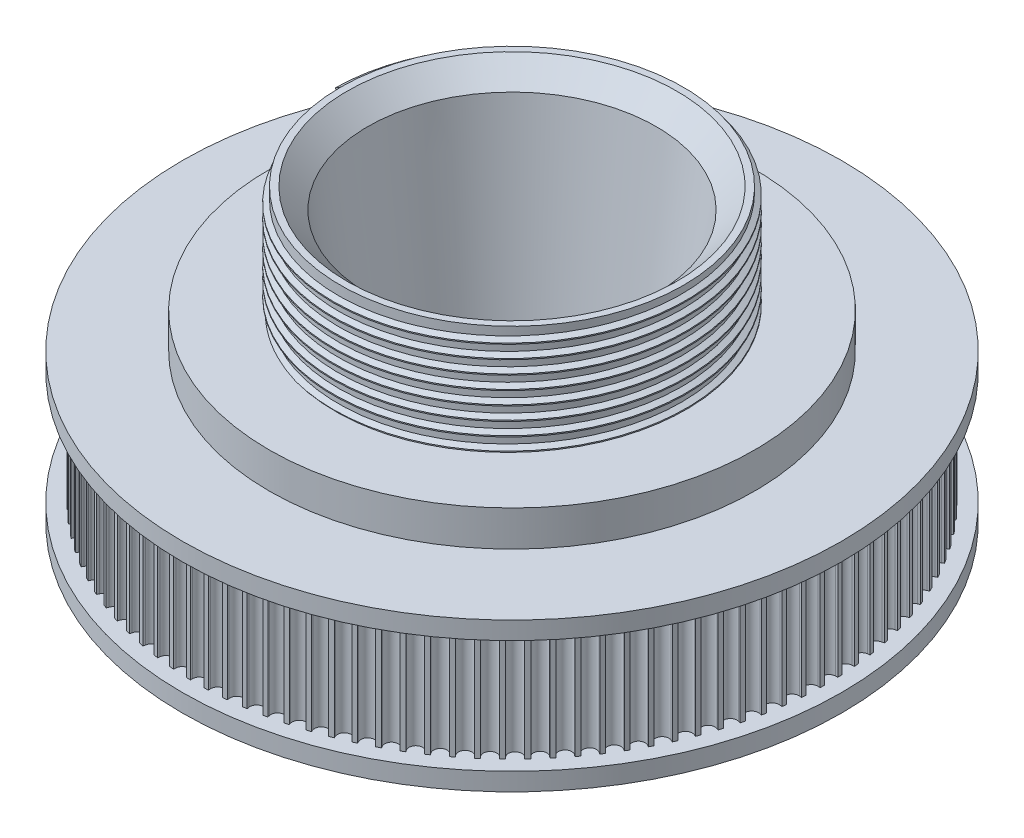
SolidWorks part; units mm, degrees
ref_plane "Front Plane" through (0, 0, 0) normal (0, 0, 1) x (1, 0, 0)
ref_plane "Top Plane" through (0, 0, 0) normal (0, 1, 0) x (1, 0, 0)
ref_plane "Right Plane" through (0, 0, 0) normal (1, 0, 0) x (0, 0, -1)
sketch "Sketch2" plane through (0, 0, 0) normal (0, 1, 0) x (1, 0, 0)
  line L2 (32.6647, -41.3108) -> (32.6647, -40.5508)
  line L3 (31.9047, -41.3108) -> (31.9047, -41.5526)
  line L5 (33.4247, -41.3108) -> (33.4247, -41.5526)
  line L6 (31.4389, -41.2976) -> (31.4252, -41.539)
  line L7 (29.9213, -41.2116) -> (29.9076, -41.453)
  line L8 (29.4569, -41.1721) -> (29.4296, -41.4123)
  line L9 (27.9467, -41.0003) -> (27.9193, -41.2406)
  line L10 (27.4853, -40.9346) -> (27.4444, -41.173)
  line L11 (25.9871, -40.6777) -> (25.9463, -40.9161)
  line L12 (25.5302, -40.586) -> (25.4759, -40.8217)
  line L13 (24.049, -40.2448) -> (23.9947, -40.4804)
  line L14 (23.598, -40.1273) -> (23.5304, -40.3595)
  line L15 (22.1384, -39.7029) -> (22.0709, -39.9351)
  line L16 (21.6948, -39.5601) -> (21.6142, -39.7881)
  line L17 (20.2616, -39.0537) -> (20.181, -39.2817)
  line L18 (19.8267, -38.8861) -> (19.7334, -39.1092)
  line L19 (18.4245, -38.2994) -> (18.3312, -38.5225)
  line L20 (17.9998, -38.1075) -> (17.894, -38.3249)
  line L21 (16.633, -37.4424) -> (16.5272, -37.6599)
  line L22 (16.2199, -37.2268) -> (16.102, -37.4379)
  line L23 (14.8929, -36.4855) -> (14.775, -36.6966)
  line L24 (14.4926, -36.2467) -> (14.3629, -36.4508)
  line L25 (13.2097, -35.4316) -> (13.08, -35.6357)
  line L26 (12.8236, -35.1706) -> (12.6826, -35.367)
  line L27 (11.5888, -34.2841) -> (11.4478, -34.4806)
  line L28 (11.2181, -34.0017) -> (11.0662, -34.1899)
  line L29 (10.0355, -33.0468) -> (9.8836, -33.235)
  line L30 (9.6813, -32.7439) -> (9.519, -32.9231)
  line L31 (8.5546, -31.7236) -> (8.3923, -31.9029)
  line L32 (8.2181, -31.4011) -> (8.0459, -31.5709)
  line L33 (7.151, -30.3188) -> (6.9788, -30.4885)
  line L34 (6.8333, -29.9778) -> (6.6517, -30.1375)
  line L35 (5.829, -28.8367) -> (5.6475, -28.9965)
  line L36 (5.5312, -28.4783) -> (5.3409, -28.6275)
  line L37 (4.5931, -27.2823) -> (4.4028, -27.4315)
  line L38 (4.316, -26.9076) -> (4.1175, -27.0458)
  line L39 (3.4471, -25.6604) -> (3.2486, -25.7987)
  line L40 (3.1916, -25.2706) -> (2.9857, -25.3974)
  line L41 (2.3946, -23.9763) -> (2.1887, -24.1031)
  line L42 (2.1616, -23.5727) -> (1.9488, -23.6876)
  line L43 (1.4392, -22.2354) -> (1.2264, -22.3503)
  line L44 (1.2293, -21.8192) -> (1.0104, -21.9219)
  line L45 (0.5837, -20.4431) -> (0.3648, -20.5458)
  line L46 (0.3978, -20.0158) -> (0.1734, -20.1059)
  line L47 (-0.169, -18.6054) -> (-0.3934, -18.6955)
  line L48 (-0.3304, -18.1682) -> (-0.5596, -18.2455)
  line L49 (-0.8165, -16.728) -> (-1.0456, -16.8053)
  line L50 (-0.953, -16.2824) -> (-1.1861, -16.3466)
  line L51 (-1.3567, -14.817) -> (-1.5899, -14.8812)
  line L52 (-1.4678, -14.3643) -> (-1.7042, -14.4153)
  line L53 (-1.788, -12.8785) -> (-2.0244, -12.9294)
  line L54 (-1.8733, -12.4203) -> (-2.1122, -12.4578)
  line L55 (-2.1089, -10.9186) -> (-2.3478, -10.9561)
  line L56 (-2.1681, -10.4564) -> (-2.4088, -10.4803)
  line L57 (-2.3184, -8.9438) -> (-2.5591, -8.9677)
  line L58 (-2.3514, -8.4789) -> (-2.593, -8.4892)
  line L59 (-2.4159, -6.9603) -> (-2.6575, -6.9706)
  line L60 (-2.4225, -6.4943) -> (-2.6643, -6.4909)
  line L61 (-2.401, -4.9744) -> (-2.6428, -4.971)
  line L62 (-2.3812, -4.5088) -> (-2.6224, -4.4917)
  line L63 (-2.2738, -2.9926) -> (-2.515, -2.9755)
  line L64 (-2.2277, -2.5288) -> (-2.4675, -2.4981)
  line L65 (-2.0346, -1.0211) -> (-2.2745, -0.9904)
  line L66 (-1.9623, -0.5607) -> (-2.2001, -0.5165)
  line L67 (-1.6843, 0.9336) -> (-1.922, 0.9779)
  line L68 (-1.5861, 1.3892) -> (-1.821, 1.4468)
  line L69 (-1.2239, 2.8655) -> (-1.4588, 2.9231)
  line L70 (-1.1001, 3.3148) -> (-1.3314, 3.3856)
  line L71 (-0.655, 4.7681) -> (-0.8863, 4.839)
  line L72 (-0.506, 5.2097) -> (-0.7329, 5.2935)
  line L73 (0.0206, 6.6356) -> (-0.2063, 6.7194)
  line L74 (0.1944, 7.068) -> (-0.0274, 7.1645)
  line L75 (0.8008, 8.4618) -> (0.579, 8.5583)
  line L76 (0.9987, 8.8838) -> (0.7828, 8.9926)
  line L77 (1.6831, 10.241) -> (1.4671, 10.3499)
  line L78 (1.9046, 10.6511) -> (1.6951, 10.772)
  line L79 (2.6646, 11.9674) -> (2.4551, 12.0883)
  line L80 (2.9089, 12.3643) -> (2.7067, 12.4968)
  line L81 (3.7422, 13.6355) -> (3.5399, 13.7681)
  line L82 (4.0086, 14.0179) -> (3.8142, 14.1617)
  line L83 (4.9124, 15.24) -> (4.718, 15.3838)
  line L84 (5.2001, 15.6067) -> (5.0141, 15.7613)
  line L85 (6.1716, 16.7757) -> (5.9856, 16.9303)
  line L86 (6.4795, 17.1256) -> (6.3026, 17.2904)
  line L87 (7.5156, 18.2377) -> (7.3387, 18.4025)
  line L88 (7.8428, 18.5696) -> (7.6755, 18.7442)
  line L89 (8.9402, 19.6213) -> (8.7729, 19.7959)
  line L90 (9.2857, 19.9342) -> (9.1285, 20.1179)
  line L91 (10.4408, 20.9221) -> (10.2836, 21.1059)
  line L92 (10.8034, 21.2149) -> (10.6569, 21.4073)
  line L93 (12.0126, 22.136) -> (11.866, 22.3283)
  line L94 (12.3912, 22.4078) -> (12.2557, 22.6081)
  line L95 (13.6505, 23.2589) -> (13.5151, 23.4593)
  line L96 (14.0439, 23.5089) -> (13.92, 23.7166)
  line L97 (15.3493, 24.2874) -> (15.2255, 24.4951)
  line L98 (15.7562, 24.5147) -> (15.6443, 24.7291)
  line L99 (17.1036, 25.2182) -> (16.9917, 25.4325)
  line L100 (17.5227, 25.4221) -> (17.4231, 25.6424)
  line L101 (18.9078, 26.0482) -> (18.8082, 26.2685)
  line L102 (19.3377, 26.228) -> (19.2507, 26.4537)
  line L103 (20.756, 26.7748) -> (20.669, 27.0004)
  line L104 (21.1954, 26.93) -> (21.1214, 27.1602)
  line L105 (22.6424, 27.3956) -> (22.5683, 27.6258)
  line L106 (23.0899, 27.5258) -> (23.0289, 27.7598)
  line L107 (24.5608, 27.9088) -> (24.4999, 28.1428)
  line L108 (25.015, 28.0134) -> (24.9674, 28.2505)
  line L109 (26.5053, 28.3126) -> (26.4577, 28.5497)
  line L110 (26.9646, 28.3914) -> (26.9305, 28.6308)
  line L111 (28.4694, 28.6058) -> (28.4353, 28.8452)
  line L112 (28.9325, 28.6584) -> (28.912, 28.8994)
  line L113 (30.447, 28.7873) -> (30.4265, 29.0283)
  line L114 (30.9123, 28.8137) -> (30.9055, 29.0554)
  line L115 (32.4317, 28.8567) -> (32.4249, 29.0984)
  line L116 (32.8978, 28.8567) -> (32.9046, 29.0984)
  line L117 (34.4172, 28.8137) -> (34.424, 29.0554)
  line L118 (34.8825, 28.7873) -> (34.903, 29.0283)
  line L119 (36.397, 28.6584) -> (36.4175, 28.8994)
  line L120 (36.8601, 28.6058) -> (36.8942, 28.8452)
  line L121 (38.3649, 28.3914) -> (38.399, 28.6308)
  line L122 (38.8242, 28.3126) -> (38.8718, 28.5497)
  line L123 (40.3145, 28.0134) -> (40.3621, 28.2505)
  line L124 (40.7687, 27.9088) -> (40.8296, 28.1428)
  line L125 (42.2396, 27.5258) -> (42.3005, 27.7598)
  line L126 (42.6871, 27.3956) -> (42.7612, 27.6258)
  line L127 (44.1341, 26.93) -> (44.2081, 27.1602)
  line L128 (44.5735, 26.7748) -> (44.6605, 27.0004)
  line L129 (45.9918, 26.228) -> (46.0787, 26.4537)
  line L130 (46.4217, 26.0482) -> (46.5213, 26.2685)
  line L131 (47.8068, 25.4221) -> (47.9064, 25.6424)
  line L132 (48.2259, 25.2182) -> (48.3378, 25.4325)
  line L133 (49.5733, 24.5147) -> (49.6852, 24.7291)
  line L134 (49.9802, 24.2874) -> (50.104, 24.4951)
  line L135 (51.2856, 23.5089) -> (51.4095, 23.7166)
  line L136 (51.679, 23.2589) -> (51.8144, 23.4593)
  line L137 (52.9383, 22.4078) -> (53.0737, 22.6081)
  line L138 (53.3169, 22.136) -> (53.4634, 22.3283)
  line L139 (54.5261, 21.2149) -> (54.6726, 21.4073)
  line L140 (54.8887, 20.9221) -> (55.0459, 21.1059)
  line L141 (56.0438, 19.9342) -> (56.201, 20.1179)
  line L142 (56.3893, 19.6213) -> (56.5566, 19.7959)
  line L143 (57.4866, 18.5696) -> (57.654, 18.7442)
  line L144 (57.8139, 18.2377) -> (57.9908, 18.4025)
  line L145 (58.85, 17.1256) -> (59.0269, 17.2904)
  line L146 (59.1579, 16.7757) -> (59.3439, 16.9303)
  line L147 (60.1294, 15.6067) -> (60.3154, 15.7613)
  line L148 (60.417, 15.24) -> (60.6115, 15.3838)
  line L149 (61.3209, 14.0179) -> (61.5153, 14.1617)
  line L150 (61.5873, 13.6355) -> (61.7895, 13.7681)
  line L151 (62.4206, 12.3643) -> (62.6228, 12.4968)
  line L152 (62.6649, 11.9674) -> (62.8743, 12.0883)
  line L153 (63.4249, 10.6511) -> (63.6343, 10.772)
  line L154 (63.6464, 10.241) -> (63.8624, 10.3499)
  line L155 (64.3307, 8.8838) -> (64.5467, 8.9926)
  line L156 (64.5287, 8.4618) -> (64.7504, 8.5583)
  line L157 (65.1351, 7.068) -> (65.3569, 7.1645)
  line L158 (65.3089, 6.6356) -> (65.5357, 6.7194)
  line L159 (65.8355, 5.2097) -> (66.0623, 5.2935)
  line L160 (65.9845, 4.7681) -> (66.2157, 4.839)
  line L161 (66.4296, 3.3148) -> (66.6608, 3.3856)
  line L162 (66.5534, 2.8655) -> (66.7883, 2.9231)
  line L163 (66.9156, 1.3892) -> (67.1504, 1.4468)
  line L164 (67.0138, 0.9336) -> (67.2515, 0.9779)
  line L165 (67.2918, -0.5607) -> (67.5296, -0.5165)
  line L166 (67.3641, -1.0211) -> (67.6039, -0.9904)
  line L167 (67.5571, -2.5288) -> (67.797, -2.4981)
  line L168 (67.6032, -2.9926) -> (67.8445, -2.9755)
  line L169 (67.7107, -4.5088) -> (67.9519, -4.4917)
  line L170 (67.7305, -4.9744) -> (67.9723, -4.971)
  line L171 (67.752, -6.4943) -> (67.9938, -6.4909)
  line L172 (67.7454, -6.9603) -> (67.987, -6.9706)
  line L173 (67.6809, -8.4789) -> (67.9225, -8.4892)
  line L174 (67.6479, -8.9438) -> (67.8886, -8.9677)
  line L175 (67.4976, -10.4564) -> (67.7382, -10.4803)
  line L176 (67.4384, -10.9186) -> (67.6773, -10.9561)
  line L177 (67.2028, -12.4203) -> (67.4417, -12.4578)
  line L178 (67.1175, -12.8785) -> (67.3539, -12.9294)
  line L179 (66.7973, -14.3643) -> (67.0337, -14.4153)
  line L180 (66.6862, -14.817) -> (66.9194, -14.8812)
  line L181 (66.2824, -16.2824) -> (66.5156, -16.3466)
  line L182 (66.146, -16.728) -> (66.3751, -16.8053)
  line L183 (65.6599, -18.1682) -> (65.8891, -18.2455)
  line L184 (65.4985, -18.6054) -> (65.7228, -18.6955)
  line L185 (64.9317, -20.0158) -> (65.1561, -20.1059)
  line L186 (64.7458, -20.4431) -> (64.9647, -20.5458)
  line L187 (64.1001, -21.8192) -> (64.3191, -21.9219)
  line L188 (63.8903, -22.2354) -> (64.1031, -22.3503)
  line L189 (63.1679, -23.5727) -> (63.3806, -23.6876)
  line L190 (62.9349, -23.9763) -> (63.1408, -24.1031)
  line L191 (62.1379, -25.2706) -> (62.3438, -25.3974)
  line L192 (61.8824, -25.6604) -> (62.0808, -25.7987)
  line L193 (61.0135, -26.9076) -> (61.2119, -27.0458)
  line L194 (60.7364, -27.2823) -> (60.9267, -27.4315)
  line L195 (59.7983, -28.4783) -> (59.9886, -28.6275)
  line L196 (59.5004, -28.8367) -> (59.682, -28.9965)
  line L197 (58.4962, -29.9778) -> (58.6777, -30.1375)
  line L198 (58.1785, -30.3188) -> (58.3507, -30.4885)
  line L199 (57.1114, -31.4011) -> (57.2836, -31.5709)
  line L200 (56.7749, -31.7236) -> (56.9372, -31.9029)
  line L201 (55.6482, -32.7439) -> (55.8105, -32.9231)
  line L202 (55.294, -33.0468) -> (55.4459, -33.235)
  line L203 (54.1114, -34.0017) -> (54.2633, -34.1899)
  line L204 (53.7406, -34.2841) -> (53.8817, -34.4806)
  line L205 (52.5059, -35.1706) -> (52.6469, -35.367)
  line L206 (52.1198, -35.4316) -> (52.2495, -35.6357)
  line L207 (50.8368, -36.2467) -> (50.9665, -36.4508)
  line L208 (50.4366, -36.4855) -> (50.5545, -36.6966)
  line L209 (49.1096, -37.2268) -> (49.2275, -37.4379)
  line L210 (48.6964, -37.4424) -> (48.8022, -37.6599)
  line L211 (47.3296, -38.1075) -> (47.4355, -38.3249)
  line L212 (46.905, -38.2994) -> (46.9983, -38.5225)
  line L213 (45.5027, -38.8861) -> (45.5961, -39.1092)
  line L214 (45.0679, -39.0537) -> (45.1484, -39.2817)
  line L215 (43.6347, -39.5601) -> (43.7153, -39.7881)
  line L216 (43.191, -39.7029) -> (43.2586, -39.9351)
  line L217 (41.7315, -40.1273) -> (41.7991, -40.3595)
  line L218 (41.2805, -40.2448) -> (41.3348, -40.4804)
  line L219 (39.7993, -40.586) -> (39.8536, -40.8217)
  line L220 (39.3424, -40.6777) -> (39.3832, -40.9161)
  line L221 (37.8442, -40.9346) -> (37.8851, -41.173)
  line L222 (37.3828, -41.0003) -> (37.4101, -41.2406)
  line L223 (35.8726, -41.1721) -> (35.8999, -41.4123)
  line L224 (35.4082, -41.2116) -> (35.4219, -41.453)
  line L225 (33.8906, -41.2976) -> (33.9043, -41.539)
  arc A22 (39.3832, -40.9161) -> (39.8536, -40.8217) centre (32.6647, -6.2308) ccw
  arc A23 (33.4247, -41.3108) -> (31.9047, -41.3108) centre (32.6647, -41.3108) ccw
  arc A24 (31.4389, -41.2976) -> (29.9213, -41.2116) centre (30.6801, -41.2546) ccw
  arc A25 (29.4569, -41.1721) -> (27.9467, -41.0003) centre (28.7018, -41.0862) ccw
  arc A26 (27.4853, -40.9346) -> (25.9871, -40.6777) centre (26.7362, -40.8062) ccw
  arc A27 (25.5302, -40.586) -> (24.049, -40.2448) centre (24.7896, -40.4154) ccw
  arc A28 (23.598, -40.1273) -> (22.1384, -39.7029) centre (22.8682, -39.9151) ccw
  arc A32 (21.6948, -39.5601) -> (20.2616, -39.0537) centre (20.9782, -39.3069) ccw
  arc A33 (19.8267, -38.8861) -> (18.4245, -38.2994) centre (19.1256, -38.5928) ccw
  arc A34 (17.9998, -38.1075) -> (16.633, -37.4424) centre (17.3164, -37.775) ccw
  arc A35 (16.2199, -37.2268) -> (14.8929, -36.4855) centre (15.5564, -36.8561) ccw
  arc A36 (14.4926, -36.2467) -> (13.2097, -35.4316) centre (13.8512, -35.8391) ccw
  arc A37 (12.8236, -35.1706) -> (11.5888, -34.2841) centre (12.2062, -34.7273) ccw
  arc A38 (11.2181, -34.0017) -> (10.0355, -33.0468) centre (10.6268, -33.5243) ccw
  arc A39 (9.6813, -32.7439) -> (8.5546, -31.7236) centre (9.1179, -32.2338) ccw
  arc A40 (8.2181, -31.4011) -> (7.151, -30.3188) centre (7.6845, -30.8599) ccw
  arc A41 (6.8333, -29.9778) -> (5.829, -28.8367) centre (6.3312, -29.4072) ccw
  arc A42 (5.5312, -28.4783) -> (4.5931, -27.2823) centre (5.0621, -27.8803) ccw
  arc A43 (4.316, -26.9076) -> (3.4471, -25.6604) centre (3.8815, -26.284) ccw
  arc A44 (3.1916, -25.2706) -> (2.3946, -23.9763) centre (2.7931, -24.6235) ccw
  arc A45 (2.1616, -23.5727) -> (1.4392, -22.2354) centre (1.8004, -22.904) ccw
  arc A46 (1.2293, -21.8192) -> (0.5837, -20.4431) centre (0.9065, -21.1312) ccw
  arc A47 (0.3978, -20.0158) -> (-0.169, -18.6054) centre (0.1144, -19.3106) ccw
  arc A48 (-0.3304, -18.1682) -> (-0.8165, -16.728) centre (-0.5735, -17.4481) ccw
  arc A49 (-0.953, -16.2824) -> (-1.3567, -14.817) centre (-1.1548, -15.5497) ccw
  arc A50 (-1.4678, -14.3643) -> (-1.788, -12.8785) centre (-1.6279, -13.6214) ccw
  arc A51 (-1.8733, -12.4203) -> (-2.1089, -10.9186) centre (-1.9911, -11.6695) ccw
  arc A52 (-2.1681, -10.4564) -> (-2.3184, -8.9438) centre (-2.2433, -9.7001) ccw
  arc A53 (-2.3514, -8.4789) -> (-2.4159, -6.9603) centre (-2.3837, -7.7196) ccw
  arc A54 (-2.4225, -6.4943) -> (-2.401, -4.9744) centre (-2.4117, -5.7344) ccw
  arc A55 (-2.3812, -4.5088) -> (-2.2738, -2.9926) centre (-2.3275, -3.7507) ccw
  arc A56 (-2.2277, -2.5288) -> (-2.0346, -1.0211) centre (-2.1311, -1.775) ccw
  arc A57 (-1.9623, -0.5607) -> (-1.6843, 0.9336) centre (-1.8233, 0.1865) ccw
  arc A58 (-1.5861, 1.3892) -> (-1.2239, 2.8655) centre (-1.405, 2.1273) ccw
  arc A59 (-1.1001, 3.3148) -> (-0.655, 4.7681) centre (-0.8776, 4.0415) ccw
  arc A60 (-0.506, 5.2097) -> (0.0206, 6.6356) centre (-0.2427, 5.9227) ccw
  arc A61 (0.1944, 7.068) -> (0.8008, 8.4618) centre (0.4976, 7.7649) ccw
  arc A62 (0.9987, 8.8838) -> (1.6831, 10.241) centre (1.3409, 9.5624) ccw
  arc A63 (1.9046, 10.6511) -> (2.6646, 11.9674) centre (2.2846, 11.3092) ccw
  arc A64 (2.9089, 12.3643) -> (3.7422, 13.6355) centre (3.3256, 12.9999) ccw
  arc A65 (4.0086, 14.0179) -> (4.9124, 15.24) centre (4.4605, 14.629) ccw
  arc A66 (5.2001, 15.6067) -> (6.1716, 16.7757) centre (5.6858, 16.1912) ccw
  arc A67 (6.4795, 17.1256) -> (7.5156, 18.2377) centre (6.9976, 17.6816) ccw
  arc A68 (7.8428, 18.5696) -> (8.9402, 19.6213) centre (8.3915, 19.0954) ccw
  arc A69 (9.2857, 19.9342) -> (10.4408, 20.9221) centre (9.8632, 20.4281) ccw
  arc A70 (10.8034, 21.2149) -> (12.0126, 22.136) centre (11.408, 21.6754) ccw
  arc A71 (12.3912, 22.4078) -> (13.6505, 23.2589) centre (13.0208, 22.8333) ccw
  arc A72 (14.0439, 23.5089) -> (15.3493, 24.2874) centre (14.6966, 23.8982) ccw
  arc A73 (15.7562, 24.5147) -> (17.1036, 25.2182) centre (16.4299, 24.8664) ccw
  arc A74 (17.5227, 25.4221) -> (18.9078, 26.0482) centre (18.2152, 25.7351) ccw
  arc A75 (19.3377, 26.228) -> (20.756, 26.7748) centre (20.0469, 26.5014) ccw
  arc A76 (21.1954, 26.93) -> (22.6424, 27.3956) centre (21.9189, 27.1628) ccw
  arc A77 (23.0899, 27.5258) -> (24.5608, 27.9088) centre (23.8253, 27.7173) ccw
  arc A78 (25.015, 28.0134) -> (26.5053, 28.3126) centre (25.7601, 28.163) ccw
  arc A79 (26.9646, 28.3914) -> (28.4694, 28.6058) centre (27.717, 28.4986) ccw
  arc A80 (28.9325, 28.6584) -> (30.447, 28.7873) centre (29.6897, 28.7229) ccw
  arc A81 (30.9123, 28.8137) -> (32.4317, 28.8567) centre (31.672, 28.8352) ccw
  arc A82 (32.8978, 28.8567) -> (34.4172, 28.8137) centre (33.6575, 28.8352) ccw
  arc A83 (34.8825, 28.7873) -> (36.397, 28.6584) centre (35.6397, 28.7229) ccw
  arc A84 (36.8601, 28.6058) -> (38.3649, 28.3914) centre (37.6125, 28.4986) ccw
  arc A85 (38.8242, 28.3126) -> (40.3145, 28.0134) centre (39.5694, 28.163) ccw
  arc A86 (40.7687, 27.9088) -> (42.2396, 27.5258) centre (41.5041, 27.7173) ccw
  arc A87 (42.6871, 27.3956) -> (44.1341, 26.93) centre (43.4106, 27.1628) ccw
  arc A88 (44.5735, 26.7748) -> (45.9918, 26.228) centre (45.2826, 26.5014) ccw
  arc A89 (46.4217, 26.0482) -> (47.8068, 25.4221) centre (47.1142, 25.7351) ccw
  arc A90 (48.2259, 25.2182) -> (49.5733, 24.5147) centre (48.8996, 24.8664) ccw
  arc A91 (49.9802, 24.2874) -> (51.2856, 23.5089) centre (50.6329, 23.8982) ccw
  arc A92 (51.679, 23.2589) -> (52.9383, 22.4078) centre (52.3087, 22.8333) ccw
  arc A93 (53.3169, 22.136) -> (54.5261, 21.2149) centre (53.9215, 21.6754) ccw
  arc A94 (54.8887, 20.9221) -> (56.0438, 19.9342) centre (55.4662, 20.4281) ccw
  arc A95 (56.3893, 19.6213) -> (57.4866, 18.5696) centre (56.938, 19.0954) ccw
  arc A96 (57.8139, 18.2377) -> (58.85, 17.1256) centre (58.3319, 17.6816) ccw
  arc A97 (59.1579, 16.7757) -> (60.1294, 15.6067) centre (59.6436, 16.1912) ccw
  arc A98 (60.417, 15.24) -> (61.3209, 14.0179) centre (60.869, 14.629) ccw
  arc A99 (61.5873, 13.6355) -> (62.4206, 12.3643) centre (62.0039, 12.9999) ccw
  arc A100 (62.6649, 11.9674) -> (63.4249, 10.6511) centre (63.0449, 11.3092) ccw
  arc A101 (63.6464, 10.241) -> (64.3307, 8.8838) centre (63.9886, 9.5624) ccw
  arc A102 (64.5287, 8.4618) -> (65.1351, 7.068) centre (64.8319, 7.7649) ccw
  arc A103 (65.3089, 6.6356) -> (65.8355, 5.2097) centre (65.5722, 5.9227) ccw
  arc A104 (65.9845, 4.7681) -> (66.4296, 3.3148) centre (66.2071, 4.0415) ccw
  arc A105 (66.5534, 2.8655) -> (66.9156, 1.3892) centre (66.7345, 2.1273) ccw
  arc A106 (67.0138, 0.9336) -> (67.2918, -0.5607) centre (67.1528, 0.1865) ccw
  arc A107 (67.3641, -1.0211) -> (67.5571, -2.5288) centre (67.4606, -1.775) ccw
  arc A108 (67.6032, -2.9926) -> (67.7107, -4.5088) centre (67.657, -3.7507) ccw
  arc A109 (67.7305, -4.9744) -> (67.752, -6.4943) centre (67.7412, -5.7344) ccw
  arc A110 (67.7454, -6.9603) -> (67.6809, -8.4789) centre (67.7131, -7.7196) ccw
  arc A111 (67.6479, -8.9438) -> (67.4976, -10.4564) centre (67.5728, -9.7001) ccw
  arc A112 (67.4384, -10.9186) -> (67.2028, -12.4203) centre (67.3206, -11.6695) ccw
  arc A113 (67.1175, -12.8785) -> (66.7973, -14.3643) centre (66.9574, -13.6214) ccw
  arc A114 (66.6862, -14.817) -> (66.2824, -16.2824) centre (66.4843, -15.5497) ccw
  arc A115 (66.146, -16.728) -> (65.6599, -18.1682) centre (65.9029, -17.4481) ccw
  arc A116 (65.4985, -18.6054) -> (64.9317, -20.0158) centre (65.2151, -19.3106) ccw
  arc A117 (64.7458, -20.4431) -> (64.1001, -21.8192) centre (64.423, -21.1312) ccw
  arc A118 (63.8903, -22.2354) -> (63.1679, -23.5727) centre (63.5291, -22.904) ccw
  arc A119 (62.9349, -23.9763) -> (62.1379, -25.2706) centre (62.5364, -24.6235) ccw
  arc A120 (61.8824, -25.6604) -> (61.0135, -26.9076) centre (61.448, -26.284) ccw
  arc A121 (60.7364, -27.2823) -> (59.7983, -28.4783) centre (60.2674, -27.8803) ccw
  arc A122 (59.5004, -28.8367) -> (58.4962, -29.9778) centre (58.9983, -29.4072) ccw
  arc A123 (58.1785, -30.3188) -> (57.1114, -31.4011) centre (57.6449, -30.8599) ccw
  arc A124 (56.7749, -31.7236) -> (55.6482, -32.7439) centre (56.2115, -32.2338) ccw
  arc A125 (55.294, -33.0468) -> (54.1114, -34.0017) centre (54.7027, -33.5243) ccw
  arc A126 (53.7406, -34.2841) -> (52.5059, -35.1706) centre (53.1233, -34.7273) ccw
  arc A127 (52.1198, -35.4316) -> (50.8368, -36.2467) centre (51.4783, -35.8391) ccw
  arc A128 (50.4366, -36.4855) -> (49.1096, -37.2268) centre (49.7731, -36.8561) ccw
  arc A129 (48.6964, -37.4424) -> (47.3296, -38.1075) centre (48.013, -37.775) ccw
  arc A130 (46.905, -38.2994) -> (45.5027, -38.8861) centre (46.2039, -38.5928) ccw
  arc A131 (45.0679, -39.0537) -> (43.6347, -39.5601) centre (44.3513, -39.3069) ccw
  arc A132 (43.191, -39.7029) -> (41.7315, -40.1273) centre (42.4613, -39.9151) ccw
  arc A133 (41.2805, -40.2448) -> (39.7993, -40.586) centre (40.5399, -40.4154) ccw
  arc A134 (39.3424, -40.6777) -> (37.8442, -40.9346) centre (38.5933, -40.8062) ccw
  arc A135 (37.3828, -41.0003) -> (35.8726, -41.1721) centre (36.6277, -41.0862) ccw
  arc A136 (35.4082, -41.2116) -> (33.8906, -41.2976) centre (34.6494, -41.2546) ccw
  arc A137 (37.4101, -41.2406) -> (37.8851, -41.173) centre (32.6647, -6.2308) ccw
  arc A138 (41.3348, -40.4804) -> (41.7991, -40.3595) centre (32.6647, -6.2308) ccw
  arc A139 (43.2586, -39.9351) -> (43.7153, -39.7881) centre (32.6647, -6.2308) ccw
  arc A140 (35.4219, -41.453) -> (35.8999, -41.4123) centre (32.6647, -6.2308) ccw
  arc A141 (33.4247, -41.5526) -> (33.9043, -41.539) centre (32.6647, -6.2308) ccw
  arc A142 (31.4252, -41.539) -> (31.9047, -41.5526) centre (32.6647, -6.2308) ccw
  arc A143 (29.4296, -41.4123) -> (29.9076, -41.453) centre (32.6647, -6.2308) ccw
  arc A144 (27.4444, -41.173) -> (27.9193, -41.2406) centre (32.6647, -6.2308) ccw
  arc A145 (25.4759, -40.8217) -> (25.9463, -40.9161) centre (32.6647, -6.2308) ccw
  arc A146 (23.5304, -40.3595) -> (23.9947, -40.4804) centre (32.6647, -6.2308) ccw
  arc A147 (45.1484, -39.2817) -> (45.5961, -39.1092) centre (32.6647, -6.2308) ccw
  arc A148 (46.9983, -38.5225) -> (47.4355, -38.3249) centre (32.6647, -6.2308) ccw
  arc A149 (48.8022, -37.6599) -> (49.2275, -37.4379) centre (32.6647, -6.2308) ccw
  arc A150 (50.5545, -36.6966) -> (50.9665, -36.4508) centre (32.6647, -6.2308) ccw
  arc A151 (52.2495, -35.6357) -> (52.6469, -35.367) centre (32.6647, -6.2308) ccw
  arc A152 (53.8817, -34.4806) -> (54.2633, -34.1899) centre (32.6647, -6.2308) ccw
  arc A153 (55.4459, -33.235) -> (55.8105, -32.9231) centre (32.6647, -6.2308) ccw
  arc A154 (56.9372, -31.9029) -> (57.2836, -31.5709) centre (32.6647, -6.2308) ccw
  arc A155 (58.3507, -30.4885) -> (58.6777, -30.1375) centre (32.6647, -6.2308) ccw
  arc A156 (59.682, -28.9965) -> (59.9886, -28.6275) centre (32.6647, -6.2308) ccw
  arc A157 (60.9267, -27.4315) -> (61.2119, -27.0458) centre (32.6647, -6.2308) ccw
  arc A158 (62.0808, -25.7987) -> (62.3438, -25.3974) centre (32.6647, -6.2308) ccw
  arc A159 (63.1408, -24.1031) -> (63.3806, -23.6876) centre (32.6647, -6.2308) ccw
  arc A160 (64.1031, -22.3503) -> (64.3191, -21.9219) centre (32.6647, -6.2308) ccw
  arc A161 (64.9647, -20.5458) -> (65.1561, -20.1059) centre (32.6647, -6.2308) ccw
  arc A162 (65.7228, -18.6955) -> (65.8891, -18.2455) centre (32.6647, -6.2308) ccw
  arc A163 (66.3751, -16.8053) -> (66.5156, -16.3466) centre (32.6647, -6.2308) ccw
  arc A164 (66.9194, -14.8812) -> (67.0337, -14.4153) centre (32.6647, -6.2308) ccw
  arc A165 (67.3539, -12.9294) -> (67.4417, -12.4578) centre (32.6647, -6.2308) ccw
  arc A166 (67.6773, -10.9561) -> (67.7382, -10.4803) centre (32.6647, -6.2308) ccw
  arc A167 (67.8886, -8.9677) -> (67.9225, -8.4892) centre (32.6647, -6.2308) ccw
  arc A168 (67.987, -6.9706) -> (67.9938, -6.4909) centre (32.6647, -6.2308) ccw
  arc A169 (67.9723, -4.971) -> (67.9519, -4.4917) centre (32.6647, -6.2308) ccw
  arc A170 (67.8445, -2.9755) -> (67.797, -2.4981) centre (32.6647, -6.2308) ccw
  arc A171 (67.6039, -0.9904) -> (67.5296, -0.5165) centre (32.6647, -6.2308) ccw
  arc A172 (67.2515, 0.9779) -> (67.1504, 1.4468) centre (32.6647, -6.2308) ccw
  arc A173 (66.7883, 2.9231) -> (66.6608, 3.3856) centre (32.6647, -6.2308) ccw
  arc A174 (66.2157, 4.839) -> (66.0623, 5.2935) centre (32.6647, -6.2308) ccw
  arc A175 (65.5357, 6.7194) -> (65.3569, 7.1645) centre (32.6647, -6.2308) ccw
  arc A176 (64.7504, 8.5583) -> (64.5467, 8.9926) centre (32.6647, -6.2308) ccw
  arc A177 (63.8624, 10.3499) -> (63.6343, 10.772) centre (32.6647, -6.2308) ccw
  arc A178 (62.8743, 12.0883) -> (62.6228, 12.4968) centre (32.6647, -6.2308) ccw
  arc A179 (61.7895, 13.7681) -> (61.5153, 14.1617) centre (32.6647, -6.2308) ccw
  arc A180 (60.6115, 15.3838) -> (60.3154, 15.7613) centre (32.6647, -6.2308) ccw
  arc A181 (59.3439, 16.9303) -> (59.0269, 17.2904) centre (32.6647, -6.2308) ccw
  arc A182 (57.9908, 18.4025) -> (57.654, 18.7442) centre (32.6647, -6.2308) ccw
  arc A183 (56.5566, 19.7959) -> (56.201, 20.1179) centre (32.6647, -6.2308) ccw
  arc A184 (55.0459, 21.1059) -> (54.6726, 21.4073) centre (32.6647, -6.2308) ccw
  arc A185 (53.4634, 22.3283) -> (53.0737, 22.6081) centre (32.6647, -6.2308) ccw
  arc A186 (51.8144, 23.4593) -> (51.4095, 23.7166) centre (32.6647, -6.2308) ccw
  arc A187 (50.104, 24.4951) -> (49.6852, 24.7291) centre (32.6647, -6.2308) ccw
  arc A188 (48.3378, 25.4325) -> (47.9064, 25.6424) centre (32.6647, -6.2308) ccw
  arc A189 (46.5213, 26.2685) -> (46.0787, 26.4537) centre (32.6647, -6.2308) ccw
  arc A190 (44.6605, 27.0004) -> (44.2081, 27.1602) centre (32.6647, -6.2308) ccw
  arc A191 (42.7612, 27.6258) -> (42.3005, 27.7598) centre (32.6647, -6.2308) ccw
  arc A192 (40.8296, 28.1428) -> (40.3621, 28.2505) centre (32.6647, -6.2308) ccw
  arc A193 (38.8718, 28.5497) -> (38.399, 28.6308) centre (32.6647, -6.2308) ccw
  arc A194 (36.8942, 28.8452) -> (36.4175, 28.8994) centre (32.6647, -6.2308) ccw
  arc A195 (34.903, 29.0283) -> (34.424, 29.0554) centre (32.6647, -6.2308) ccw
  arc A196 (32.9046, 29.0984) -> (32.4249, 29.0984) centre (32.6647, -6.2308) ccw
  arc A197 (30.9055, 29.0554) -> (30.4265, 29.0283) centre (32.6647, -6.2308) ccw
  arc A198 (28.912, 28.8994) -> (28.4353, 28.8452) centre (32.6647, -6.2308) ccw
  arc A199 (26.9305, 28.6308) -> (26.4577, 28.5497) centre (32.6647, -6.2308) ccw
  arc A200 (24.9674, 28.2505) -> (24.4999, 28.1428) centre (32.6647, -6.2308) ccw
  arc A201 (23.0289, 27.7598) -> (22.5683, 27.6258) centre (32.6647, -6.2308) ccw
  arc A202 (21.1214, 27.1602) -> (20.669, 27.0004) centre (32.6647, -6.2308) ccw
  arc A203 (19.2507, 26.4537) -> (18.8082, 26.2685) centre (32.6647, -6.2308) ccw
  arc A204 (17.4231, 25.6424) -> (16.9917, 25.4325) centre (32.6647, -6.2308) ccw
  arc A205 (15.6443, 24.7291) -> (15.2255, 24.4951) centre (32.6647, -6.2308) ccw
  arc A206 (13.92, 23.7166) -> (13.5151, 23.4593) centre (32.6647, -6.2308) ccw
  arc A207 (12.2557, 22.6081) -> (11.866, 22.3283) centre (32.6647, -6.2308) ccw
  arc A208 (10.6569, 21.4073) -> (10.2836, 21.1059) centre (32.6647, -6.2308) ccw
  arc A209 (9.1285, 20.1179) -> (8.7729, 19.7959) centre (32.6647, -6.2308) ccw
  arc A210 (7.6755, 18.7442) -> (7.3387, 18.4025) centre (32.6647, -6.2308) ccw
  arc A211 (6.3026, 17.2904) -> (5.9856, 16.9303) centre (32.6647, -6.2308) ccw
  arc A212 (5.0141, 15.7613) -> (4.718, 15.3838) centre (32.6647, -6.2308) ccw
  arc A213 (3.8142, 14.1617) -> (3.5399, 13.7681) centre (32.6647, -6.2308) ccw
  arc A214 (1.0104, -21.9219) -> (1.2264, -22.3503) centre (32.6647, -6.2308) ccw
  arc A215 (0.1734, -20.1059) -> (0.3648, -20.5458) centre (32.6647, -6.2308) ccw
  arc A216 (-0.5596, -18.2455) -> (-0.3934, -18.6955) centre (32.6647, -6.2308) ccw
  arc A217 (-1.1861, -16.3466) -> (-1.0456, -16.8053) centre (32.6647, -6.2308) ccw
  arc A218 (-1.7042, -14.4153) -> (-1.5899, -14.8812) centre (32.6647, -6.2308) ccw
  arc A219 (-2.1122, -12.4578) -> (-2.0244, -12.9294) centre (32.6647, -6.2308) ccw
  arc A220 (-2.4088, -10.4803) -> (-2.3478, -10.9561) centre (32.6647, -6.2308) ccw
  arc A221 (-2.593, -8.4892) -> (-2.5591, -8.9677) centre (32.6647, -6.2308) ccw
  arc A222 (-2.6643, -6.4909) -> (-2.6575, -6.9706) centre (32.6647, -6.2308) ccw
  arc A223 (-2.6224, -4.4917) -> (-2.6428, -4.971) centre (32.6647, -6.2308) ccw
  arc A224 (-2.4675, -2.4981) -> (-2.515, -2.9755) centre (32.6647, -6.2308) ccw
  arc A225 (-2.2001, -0.5165) -> (-2.2745, -0.9904) centre (32.6647, -6.2308) ccw
  arc A226 (-1.821, 1.4468) -> (-1.922, 0.9779) centre (32.6647, -6.2308) ccw
  arc A227 (-1.3314, 3.3856) -> (-1.4588, 2.9231) centre (32.6647, -6.2308) ccw
  arc A228 (-0.7329, 5.2935) -> (-0.8863, 4.839) centre (32.6647, -6.2308) ccw
  arc A229 (-0.0274, 7.1645) -> (-0.2063, 6.7194) centre (32.6647, -6.2308) ccw
  arc A230 (0.7828, 8.9926) -> (0.579, 8.5583) centre (32.6647, -6.2308) ccw
  arc A231 (2.7067, 12.4968) -> (2.4551, 12.0883) centre (32.6647, -6.2308) ccw
  arc A232 (1.6951, 10.772) -> (1.4671, 10.3499) centre (32.6647, -6.2308) ccw
  arc A233 (1.9488, -23.6876) -> (2.1887, -24.1031) centre (32.6647, -6.2308) ccw
  arc A234 (2.9857, -25.3974) -> (3.2486, -25.7987) centre (32.6647, -6.2308) ccw
  arc A235 (4.1175, -27.0458) -> (4.4028, -27.4315) centre (32.6647, -6.2308) ccw
  arc A236 (5.3409, -28.6275) -> (5.6475, -28.9965) centre (32.6647, -6.2308) ccw
  arc A237 (6.6517, -30.1375) -> (6.9788, -30.4885) centre (32.6647, -6.2308) ccw
  arc A238 (8.0459, -31.5709) -> (8.3923, -31.9029) centre (32.6647, -6.2308) ccw
  arc A239 (9.519, -32.9231) -> (9.8836, -33.235) centre (32.6647, -6.2308) ccw
  arc A240 (11.0662, -34.1899) -> (11.4478, -34.4806) centre (32.6647, -6.2308) ccw
  arc A241 (12.6826, -35.367) -> (13.08, -35.6357) centre (32.6647, -6.2308) ccw
  arc A242 (14.3629, -36.4508) -> (14.775, -36.6966) centre (32.6647, -6.2308) ccw
  arc A243 (16.102, -37.4379) -> (16.5272, -37.6599) centre (32.6647, -6.2308) ccw
  arc A244 (17.894, -38.3249) -> (18.3312, -38.5225) centre (32.6647, -6.2308) ccw
  arc A245 (21.6142, -39.7881) -> (22.0709, -39.9351) centre (32.6647, -6.2308) ccw
  arc A246 (19.7334, -39.1092) -> (20.181, -39.2817) centre (32.6647, -6.2308) ccw
  dimension "D2" = 70.66
  dimension "D3" = 0.76
  dimension "D1" = 111
extrude "Boss-Extrude1" add sketch "Sketch2" along normal blind 10 and the other way blind 2.7 contours L20 A244 L19 A33 L18 A246 L17 A32 L16 A245 L15 A28 L14 A146 L13 A27 L12 A145 L11 A26 L10 A144 L9 A25 L8 A143 L7 A24 L6 A142 L3 A23 L5 A141 L225 A136 L224 A140 L223 A135 L222 A137 L221 A134 L220 A22 L219 A133 L218 A138 L217 A132 L216 A139 L215 A131 L214 A147 L213 A130 L212 A148 L211 A129 L210 A149 L209 A128 L208 A150 L207 A127 L206 A151 L205 A126 L204 A152 L203 A125 L202 A153 L201 A124 L200 A154 L199 A123 L198 A155 L197 A122 L196 A156 L195 A121 L194 A157 L193 A120 L192 A158 L191 A119 L190 A159 L189 A118 L188 A160 L187 A117 L186 A161 L185 A116 L184 A162 L183 A115 L182 A163 L181 A114 L180 A164 L179 A113 L178 A165 L177 A112 L176 A166 L175 A111 L174 A167 L173 A110 L172 A168 L171 A109 L170 A169 L169 A108 L168 A170 L167 A107 L166 A171 L165 A106 L164 A172 L163 A105 L162 A173 L161 A104 L160 A174 L159 A103 L158 A175 L157 A102 L156 A176 L155 A101 L154 A177 L153 A100 L152 A178 L151 A99 L150 A179 L149 A98 L148 A180 L147 A97 L146 A181 L145 A96 L144 A182 L143 A95 L142 A183 L141 A94 L140 A184 L139 A93 L138 A185 L137 A92 L136 A186 L135 A91 L134 A187 L133 A90 L132 A188 L131 A89 L130 A189 L129 A88 L128 A190 L127 A87 L126 A191 L125 A86 L124 A192 L123 A85 L122 A193 L121 A84 L120 A194 L119 A83 L118 A195 L117 A82 L116 A196 L115 A81 L114 A197 L113 A80 L112 A198 L111 A79 L110 A199 L109 A78 L108 A200 L107 A77 L106 A201 L105 A76 L104 A202 L103 A75 L102 A203 L101 A74 L100 A204 L99 A73 L98 A205 L97 A72 L96 A206 L95 A71 L94 A207 L93 A70 L92 A208 L91 A69 L90 A209 L89 A68 L88 A210 L87 A67 L86 A211 L85 A66 L84 A212 L83 A65 L82 A213 L81 A64 L80 A231 L79 A63 L78 A232 L77 A62 L76 A230 L75 A61 L74 A229 L73 A60 L72 A228 L71 A59 L70 A227 L69 A58 L68 A226 L67 A57 L66 A225 L65 A56 L64 A224 L63 A55 L62 A223 L61 A54 L60 A222 L59 A53 L58 A221 L57 A52 L56 A220 L55 A51 L54 A219 L53 A50 L52 A218 L51 A49 L50 A217 L49 A48 L48 A216 L47 A47 L46 A215 L45 A46 L44 A214 L43 A45 L42 A233 L41 A44 L40 A234 L39 A43 L38 A235 L37 A42 L36 A236 L35 A41 L34 A237 L33 A40 L32 A238 L31 A39 L30 A239 L29 A38 L28 A240 L27 A37 L26 A241 L25 A36 L24 A242 L23 A35 L22 A243 L21 A34
sketch "Sketch3" plane through (0, 10, 0) normal (0, 1, 0) x (1, 0, 0)
  circle A0 centre (32.6647, -6.2308) radius 19.25
  dimension "D2" = 38.5
extrude "Boss-Extrude2" add sketch "Sketch3" along normal blind 18 contours A0 | A0 | A0 | A0 region at (32.6647, 10, 6.2308)
thread "Thread1" pitch 1 method extrude profile "Thread Profile1" start angle 0, offset 0, length 12, pitch 1.5, diameter 38.5
ref_plane "Plane1" through (13.4147, 28, 6.2308) normal (0, 0, 1) x (-1, 0, 0)
sketch "Thread Profile1" plane through (13.4147, 28, 6.2308) normal (0, 0, 1) x (-1, 0, 0)
  line L0 (0, 0) -> (0, 1) construction
  line L1 (0, 0) -> (0.5413, 0.3125)
  line L2 (0.5413, 0.3125) -> (0.5413, 0.4375)
  line L3 (0.5413, 0.4375) -> (0, 0.75)
  line L4 (0.5413, 0.375) -> (0, 0.375) construction
  line L11 (0, 0) -> (0, 0.75)
  point P2 (0, 0)
  dimension "Pitch" = 1
  dimension "Profile_Angle" = 60
  dimension "Profile_Land" = 0.125
  dimension "Profile_Height" = 0.5413
sketch "Sketch10" plane through (0, -2.7, 0) normal (0, -1, 0) x (1, 0, 0)
  circle A5 centre (32.6647, 6.2308) radius 37
  circle A6 centre (32.6647, 6.2308) radius 30
  dimension "D1" = 74
  dimension "D2" = 60
extrude "Boss-Extrude3" add sketch "Sketch10" along normal blind 2 contours A5 A6 region at (-3.2887, -2.7, 6.2308)
chamfer "Chamfer7" distance 2 angle 45 1 edges at (32.6647, -4.7, -23.7692)
sketch "Sketch11" plane through (0, 10, 0) normal (0, 1, 0) x (1, 0, 0)
  circle A421 centre (32.6647, -6.2308) radius 37 construction
  circle A422 centre (32.6647, -6.2308) radius 37
extrude "Boss-Extrude5" add sketch "Sketch11" along normal blind 2
sketch "Sketch12" plane through (0, 12, 0) normal (0, 1, 0) x (1, 0, 0)
  circle A0 centre (32.6647, -6.2308) radius 19.25 construction
  circle A1 centre (32.6647, -6.2308) radius 19.25
  circle A2 centre (32.6647, -6.2308) radius 27.25
  dimension "D1" = 8
extrude "Boss-Extrude6" add sketch "Sketch12" along normal blind 4
sketch "Sketch13" plane through (0, -2.7, 0) normal (0, -1, 0) x (1, 0, 0)
  line L0 (32.6647, 6.2308) -> (45.1647, 6.2308) construction
  circle A0 centre (32.6647, 6.2308) radius 12.5
  circle A1 centre (32.6647, 6.2308) radius 16.5 construction
  dimension "D2" = 4
  dimension "D1" = 33
sketch "Sketch14" plane through (0, 28, 0) normal (0, 1, 0) x (1, 0, 0)
  line L0 (32.6647, -6.2308) -> (49.1647, -6.2308)
  circle A0 centre (32.6647, -6.2308) radius 16.5
  circle A1 centre (32.6647, -6.2308) radius 19.25
  circle A2 centre (32.6647, -6.2308) radius 19.25
  dimension "D2" = 33
  dimension "D1" = 0
loft "Cut-Loft1" cut section "Sketch13" section "Sketch14" connector at (45.1647, -2.7, 6.2163) connector at (49.1647, 28, 6.2312)
chamfer "Chamfer8" distance 2 angle 45 1 edges at (32.6647, 28, 22.7308) first distance on face at (32.6647, 28, 22.7308)
ref_plane "Plane2" through (0, 0.8, 0) normal (0, -1, 0) x (-1, 0, 0)
sketch "Sketch15" plane through (0, 0.8, 0) normal (0, -1, 0) x (-1, 0, 0)
  circle A0 centre (-32.6647, -6.2308) radius 12.5 construction
  circle A1 centre (-32.6647, -6.2308) radius 12.5
  circle A2 centre (-32.6647, -6.2308) radius 12.5
  dimension "D1" = 25
